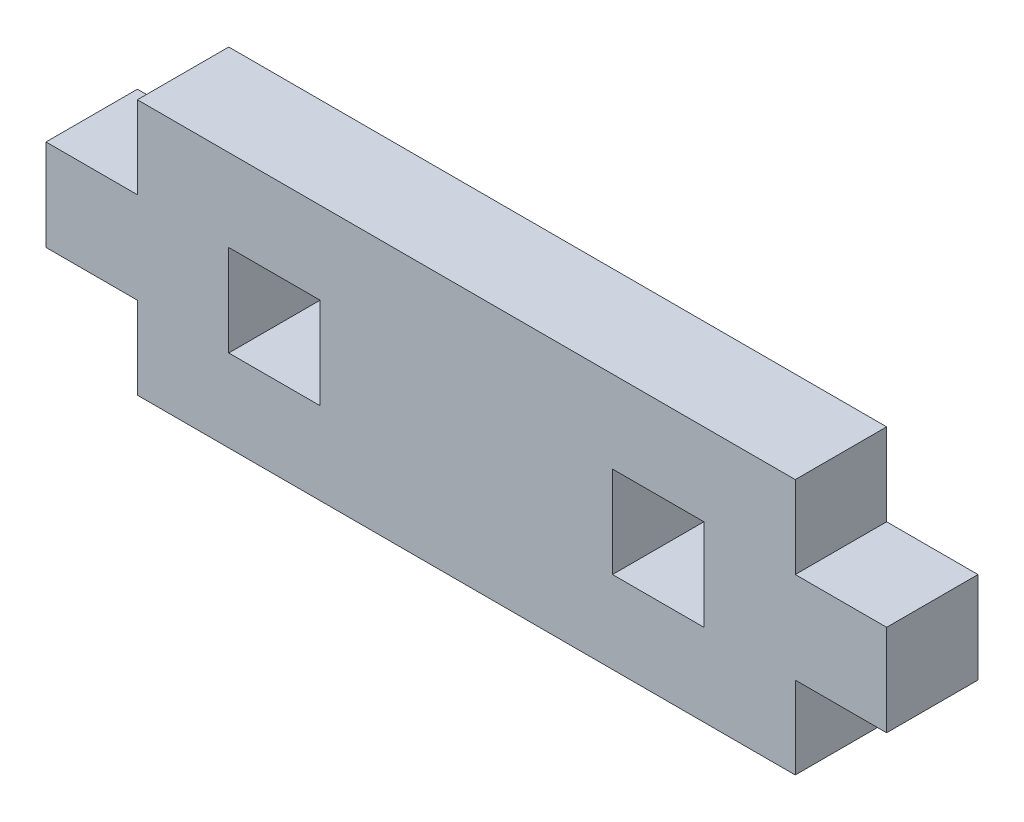
SolidWorks part; units mm, degrees
ref_plane "Front Plane" through (0, 0, 0) normal (0, 0, 1) x (1, 0, 0)
ref_plane "Top Plane" through (0, 0, 0) normal (0, 1, 0) x (1, 0, 0)
ref_plane "Right Plane" through (0, 0, 0) normal (1, 0, 0) x (0, 0, -1)
sketch "Sketch2" plane through (0, 0, 0) normal (0, 0, 1) x (1, 0, 0)
  line L0 (0, 4.5) -> (0, 9.5)
  line L1 (0, -2.75) -> (0, 2.75) construction
  line L2 (0, 9.5) -> (5, 9.5)
  line L3 (5, 9.5) -> (5, 14)
  line L4 (2.75, 0) -> (-2.75, 0) construction
  line L5 (5, 0) -> (41, 0)
  line L6 (41, 9.5) -> (41, 14)
  line L7 (41, 9.5) -> (46, 9.5)
  line L8 (46, 9.5) -> (46, 4.5)
  line L9 (46, 4.5) -> (41, 4.5)
  line L10 (41, 0) -> (41, 4.5)
  line L11 (41, 14) -> (5, 14)
  line L12 (5, 0) -> (5, 4.5)
  line L13 (5, 4.5) -> (0, 4.5)
  dimension "D1" = 36
  dimension "D2" = 5
  dimension "D3" = 14
  dimension "D4" = 5
extrude "Boss-Extrude1" add sketch "Sketch2" along normal blind 5
sketch "Sketch3" plane through (0, 0, 5) normal (0, 0, 1) x (1, 0, 0)
  line L1 (41, 14) -> (5, 14) construction
  line L2 (10, 9.5) -> (10, 4.5)
  line L4 (15, 4.5) -> (10, 4.5)
  line L5 (31, 9.5) -> (36, 9.5)
  line L6 (31, 9.5) -> (31, 4.5)
  line L7 (31, 4.5) -> (36, 4.5)
  line L8 (36, 9.5) -> (36, 4.5)
  line L9 (15, 9.5) -> (15, 4.5)
  line L10 (15, 9.5) -> (10, 9.5)
  line L11 (5, 4.5) -> (5, 0) construction
  line L12 (23, 14) -> (23, -3.9207) construction
  line L13 (41, 9.5) -> (41, 14) construction
  dimension "D1" = 5
  dimension "D2" = 5
  dimension "D3" = 16
extrude "Cut-Extrude1" cut sketch "Sketch3" against normal through all
